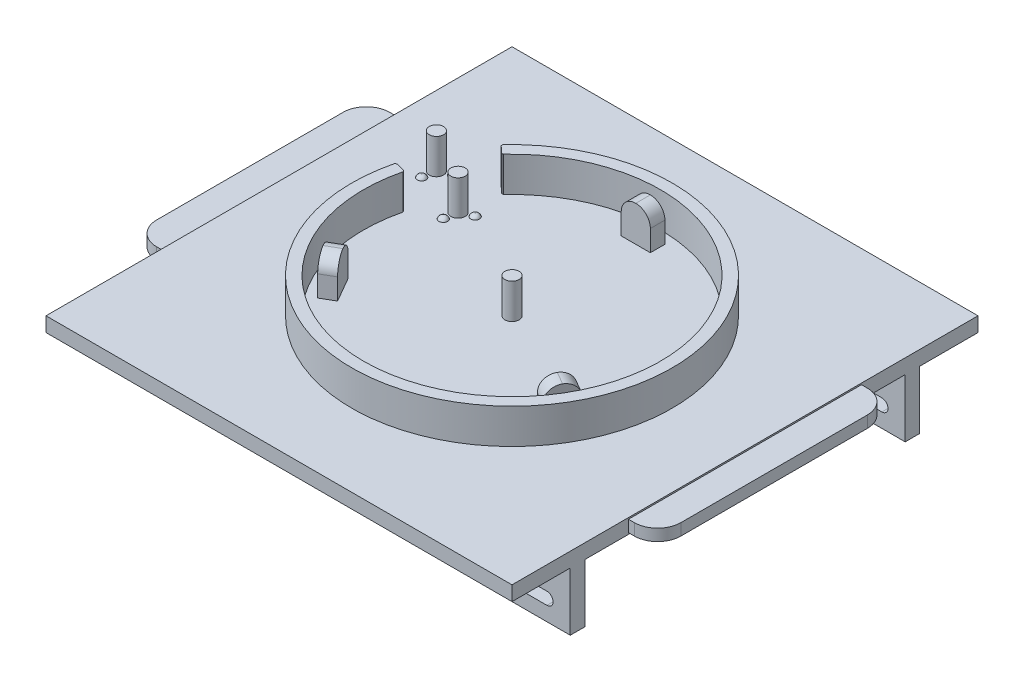
SolidWorks part; units mm, degrees
ref_plane "Vorne" through (0, 0, 0) normal (0, 0, 1) x (1, 0, 0)
ref_plane "Oben" through (0, 0, 0) normal (0, 1, 0) x (1, 0, 0)
ref_plane "Seite" through (0, 0, 0) normal (1, 0, 0) x (0, 0, -1)
sketch "Skizze1" plane through (0, 0, 0) normal (0, 1, 0) x (1, 0, 0)
  line L1 (80, -80) -> (-80, -80)
  line L2 (80, -80) -> (80, 80)
  line L3 (80, 80) -> (-80, 80)
  line L4 (-80, -80) -> (-80, 80)
  line L5 (80, -80) -> (-80, 80) construction
  line L6 (80, 80) -> (-80, -80) construction
  point P0 (0, 0)
  dimension "D1" = 160
extrude "Aufsatz-Linear austragen1" add sketch "Skizze1" along normal mid plane 5
sketch "Skizze2" plane through (0, -2.5, 0) normal (0, -1, 0) x (-1, 0, 0)
  line L0 (-80, 0) -> (80, 0) construction
  line L5 (80, -57.5) -> (-80, -57.5) construction
  line L6 (80, 55) -> (-80, 55)
  line L7 (80, 55) -> (80, 60)
  line L8 (80, 60) -> (-80, 60)
  line L9 (-80, 55) -> (-80, 60)
  line L10 (0, 60) -> (0, 55) construction
  line L15 (-80, -80) -> (-80, 80) construction
  line L16 (80, 80) -> (80, -80) construction
  line L17 (0, -80) -> (0, 80) construction
  line L18 (80, -80) -> (-80, -80) construction
  line L19 (-80, 80) -> (80, 80) construction
  line L20 (80, 57.5) -> (-80, 57.5) construction
  line L21 (0, -60) -> (0, -55) construction
  line L22 (-80, -55) -> (-80, -60)
  line L23 (80, -60) -> (-80, -60)
  line L24 (80, -55) -> (80, -60)
  line L25 (80, -55) -> (-80, -55)
  point P28 (0, -57.5)
  point P672 (0, 57.5)
  dimension "D1" = 160
  dimension "D2" = 5
  dimension "D3" = 60
extrude "Aufsatz-Linear austragen2" add sketch "Skizze2" along normal blind 20
sketch "Skizze3" plane through (0, 0, 0) normal (0, 0, 1) x (1, 0, 0)
  line L0 (25, -13.4) -> (72, -13.4)
  line L1 (25, -17.6) -> (72, -17.6)
  line L2 (80, -22.5) -> (-80, -22.5) construction
  line L3 (80, -22.5) -> (80, -2.5) construction
  line L4 (-80, -22.5) -> (-80, -2.5) construction
  line L5 (-3.7, -22.5) -> (3.7, -22.5)
  circle A0 centre (-72, -15.5) radius 2.1
  arc A1 (72, -17.6) -> (72, -13.4) centre (72, -15.5) ccw
  arc A2 (25, -13.4) -> (25, -17.6) centre (25, -15.5) ccw
  arc A3 (3.7, -22.5) -> (-3.7, -22.5) centre (0, -22.5) ccw
  dimension "D2" = 4.2
  dimension "D6" = 3.7
  dimension "D1" = 7
  dimension "D3" = 47
  dimension "D4" = 8
  dimension "D5" = 8
extrude "Schnitt-Linear austragen1" cut sketch "Skizze3" against normal through all both and the other way through all
sketch "Skizze4" plane through (0, 2.5, 0) normal (0, 1, 0) x (1, 0, 0)
  line L0 (-49.4361, 12.5326) -> (-53.3135, 13.5156)
  line L1 (-80, 80) -> (-80, -80) construction
  line L2 (-37.7606, 34.2803) -> (-40.7222, 36.9689)
  line L3 (-49.4361, 12.5326) -> (-40, 21.4746) construction
  line L4 (-40, 21.4746) -> (-37.7606, 34.2803) construction
  line L5 (0, 0) -> (-40, 21.4746) construction
  line L6 (-40, 21.4746) -> (-80, 42.9493) construction
  circle A0 centre (0, 0) radius 2.45
  circle A3 centre (-40, 21.4746) radius 2.45
  arc A4 (-53.3135, 13.5156) -> (-40.7222, 36.9689) centre (0, 0) ccw
  arc A5 (-49.4361, 12.5326) -> (-37.7606, 34.2803) centre (0, 0) ccw
  circle A6 centre (-56.0352, 30.0834) radius 2.45
  dimension "D1" = 4.9
  dimension "D4" = 18.2
  dimension "D6" = 13
  dimension "D3" = 40
  dimension "55" = 55
  dimension "D5" = 51
  dimension "D2" = 45.4
extrude "Aufsatz-Linear austragen3" add sketch "Skizze4" along normal blind 12
chamfer "Fase1" distance 0.4 angle 45 4 edges at (-49.4361, 8.5, -12.5326) (-53.3135, 8.5, -13.5156) (-40.7222, 8.5, -36.9689) (-37.7606, 8.5, -34.2803)
sketch "Skizze6" plane through (0, 2.5, 0) normal (0, 1, 0) x (1, 0, 0)
  line L0 (0, 45) -> (-38.9711, -22.5) construction
  line L1 (-38.9711, -22.5) -> (38.9711, -22.5) construction
  line L2 (38.9711, -22.5) -> (0, 45) construction
  line L3 (0, 0) -> (-38.9711, -22.5) construction
  line L4 (0, 0) -> (38.9711, -22.5) construction
  line L5 (0, 0) -> (0, 45) construction
  line L6 (43.6362, -19.4199) -> (39.3061, -16.9199)
  line L7 (39.3061, -16.9199) -> (34.3061, -25.5801)
  line L8 (34.3061, -25.5801) -> (38.6362, -28.0801)
  line L9 (38.6362, -28.0801) -> (43.6362, -19.4199)
  line L10 (-34.3061, -25.5801) -> (-39.3061, -16.9199)
  line L11 (-39.3061, -16.9199) -> (-43.6362, -19.4199)
  line L12 (-43.6362, -19.4199) -> (-38.6362, -28.0801)
  line L13 (-38.6362, -28.0801) -> (-34.3061, -25.5801)
  line L14 (5, 42.5) -> (-5, 42.5)
  line L15 (-5, 42.5) -> (-5, 47.5)
  line L16 (-5, 47.5) -> (5, 47.5)
  line L17 (5, 47.5) -> (5, 42.5)
  line L18 (5, 47.5) -> (-5, 42.5) construction
  line L19 (-5, 47.5) -> (5, 42.5) construction
  line L20 (39.3061, -16.9199) -> (38.6362, -28.0801) construction
  line L21 (34.3061, -25.5801) -> (43.6362, -19.4199) construction
  line L22 (-38.6362, -28.0801) -> (-39.3061, -16.9199) construction
  line L23 (-43.6362, -19.4199) -> (-34.3061, -25.5801) construction
  circle A0 centre (0, 0) radius 45 construction
  point P3 (-38.9711, -22.5)
  point P4 (0, 45)
  point P5 (38.9711, -22.5)
  point P19 (0, 45)
  point P22 (38.9711, -22.5)
  point P23 (-38.9711, -22.5)
  dimension "D1" = 90
  dimension "D2" = 10
  dimension "D3" = 5
extrude "Aufsatz-Linear austragen4" add sketch "Skizze6" along normal blind 12.2 separate body
fillet "Verrundung1" radius 5 2 edges at (36.4711, 14.7, 26.8301) (41.4711, 14.7, 18.1699)
fillet "Verrundung2" radius 5 2 edges at (-36.4711, 14.7, 26.8301) (-41.4711, 14.7, 18.1699)
fillet "Verrundung3" radius 5 2 edges at (-5, 14.7, -45) (5, 14.7, -45)
sketch "Skizze7" plane through (0, 0, 0) normal (0, 1, 0) x (1, 0, 0)
  line L0 (-80, 40) -> (-90, 40)
  line L1 (-80, 80) -> (-80, -80) construction
  line L2 (-90, 40) -> (-90, -40)
  line L3 (-90, -40) -> (-80, -40)
  line L4 (80, 80) -> (-80, 80) construction
  line L5 (-80, 40) -> (-80, -40)
  line L6 (0, -50) -> (0, 50) construction
  line L7 (80, 40) -> (80, -40)
  line L8 (90, -40) -> (80, -40)
  line L9 (90, 40) -> (90, -40)
  line L10 (80, 40) -> (90, 40)
  dimension "D1" = 80
  dimension "D2" = 10
  dimension "D3" = 40
extrude "Aufsatz-Linear austragen5" add sketch "Skizze7" along normal mid plane 4
fillet "Verrundung4" radius 8 4 edges at (90, 0, 40) (90, 0, -40) (-90, 0, -40) (-90, 0, 40)
sketch "Skizze8" plane through (0, 2.5, 0) normal (0, 1, 0) x (1, 0, 0)
  line L0 (-51.8721, 31.7917) -> (-56.6374, 25.6239) construction
  line L1 (-56.6374, 25.6239) -> (-59.5962, 32.8347) construction
  line L2 (-59.5962, 32.8347) -> (-51.8721, 31.7917) construction
  line L3 (-43.561, 24.2259) -> (-40.6022, 17.0151) construction
  line L4 (-40.6022, 17.0151) -> (-35.8369, 23.1829) construction
  line L5 (-35.8369, 23.1829) -> (-43.561, 24.2259) construction
  circle A0 centre (-40, 21.4746) radius 4.5 construction
  circle A1 centre (-56.0352, 30.0834) radius 4.5 construction
  circle A2 centre (-59.5962, 32.8347) radius 1.5
  circle A3 centre (-56.6374, 25.6239) radius 1.5
  circle A4 centre (-51.8721, 31.7917) radius 1.5
  circle A5 centre (-43.561, 24.2259) radius 1.5
  circle A6 centre (-40.6022, 17.0151) radius 1.5
  circle A7 centre (-35.8369, 23.1829) radius 1.5
  point P18 (0, 0)
  dimension "D2" = 12
  dimension "D1" = 9
  dimension "D3" = 3
extrude "Aufsatz-Linear austragen6" add sketch "Skizze8" along normal mid plane 2
fillet "Verrundung5" radius 1.5 6 edges at (-40.6022, 3.5, -15.5151) (-35.8369, 3.5, -21.6829) (-51.8721, 3.5, -30.2917) (-43.561, 3.5, -22.7259) (-56.6374, 3.5, -24.1239) (-59.5962, 3.5, -31.3347)
